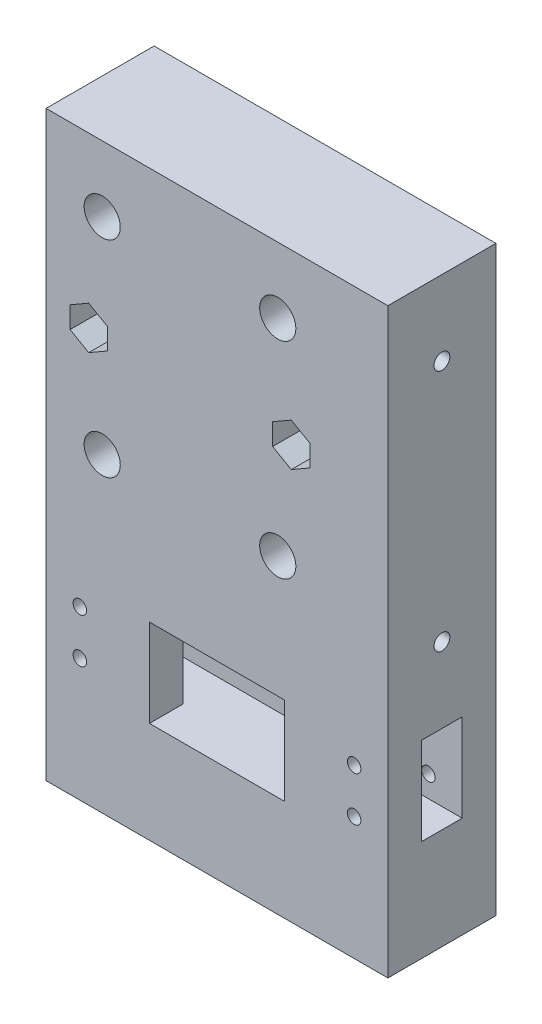
SolidWorks part; units mm, degrees
other "Markup1"
sketch "Sketch8" plane through (21.3115, 25, 0) normal (0.306, 0.1864, -0.9336) x (-0.9512, 0.0181, -0.3081)
ref_plane "Front Plane" through (0, 0, 0) normal (0, 0, 1) x (1, 0, 0)
ref_plane "Top Plane" through (0, 0, 0) normal (0, 1, 0) x (1, 0, 0)
ref_plane "Right Plane" through (0, 0, 0) normal (1, 0, 0) x (0, 0, -1)
sketch "Sketch1" plane through (0, 0, 0) normal (0, 0, 1) x (1, 0, 0)
  line L0 (0, 25) -> (0, -25) construction
  line L1 (21.3115, 25) -> (-21.3115, 25)
  line L2 (21.3115, 25) -> (21.3115, -25)
  line L3 (21.3115, -25) -> (-21.3115, -25)
  line L4 (-21.3115, 25) -> (-21.3115, -25)
  line L5 (21.3115, 25) -> (-21.3115, -25) construction
  line L6 (21.3115, -25) -> (-21.3115, 25) construction
  line L7 (-21.3115, 0) -> (21.3115, 0) construction
  circle A0 centre (-13, -15.25) radius 2.677
  circle A1 centre (13, -15.25) radius 2.677
  circle A2 centre (13, 15.25) radius 2.677
  circle A3 centre (-13, 15.25) radius 2.677
  point P0 (0, 0)
  dimension "D1" = 30.5
  dimension "D2" = 26
  dimension "D3" = 50
extrude "Boss-Extrude1" add sketch "Sketch1" along normal blind 16
sketch "Sketch2" plane through (0, 0, 0) normal (0, 0, 1) x (1, 0, 0)
  circle A0 centre (0, 0) radius 11
  dimension "D1" = 22
extrude "Cut-Extrude2" cut sketch "Sketch2" along normal blind 11
sketch "Sketch3" plane through (0, 0, 0) normal (0, 0, -1) x (-1, 0, 0)
  line L0 (0, 0) -> (-18.0234, 0) construction
  line L1 (0, 0) -> (0, 5.0894) construction
  circle A0 centre (-15, 0) radius 1.75
  circle A1 centre (15, 0) radius 1.75
  dimension "D1" = 15
  dimension "D2" = 3.5
extrude "Cut-Extrude3" cut sketch "Sketch3" against normal blind 10
sketch "Sketch9" plane through (0, 0, 0) normal (0, 0, -1) x (-1, 0, 0)
  line L0 (0, -11) -> (0, 11) construction
  line L1 (-15, 3.1754) -> (-17.75, 1.5877)
  line L2 (-17.75, 1.5877) -> (-17.75, -1.5877)
  line L3 (-17.75, -1.5877) -> (-15, -3.1754)
  line L4 (-15, -3.1754) -> (-12.25, -1.5877)
  line L5 (-12.25, -1.5877) -> (-12.25, 1.5877)
  line L6 (-12.25, 1.5877) -> (-15, 3.1754)
  line L7 (12.25, 1.5877) -> (15, 3.1754)
  line L8 (12.25, -1.5877) -> (12.25, 1.5877)
  line L9 (15, -3.1754) -> (12.25, -1.5877)
  line L10 (17.75, -1.5877) -> (15, -3.1754)
  line L11 (17.75, 1.5877) -> (17.75, -1.5877)
  line L12 (15, 3.1754) -> (17.75, 1.5877)
  circle A0 centre (-15, 0) radius 2.75 construction
  circle A1 centre (0, 0) radius 11 construction
  point P1 (-17.75, 0)
  dimension "D1" = 5.5
extrude "Cut-Extrude6" cut sketch "Sketch9" against normal through all from offset 5 offset against normal yes
sketch "Sketch30" plane through (0, -25, 0) normal (0, -1, 0) x (1, 0, 0)
  line L1 (-21.3115, 16) -> (21.3115, 16)
  line L2 (-21.3115, 16) -> (-21.3115, 0)
  line L3 (-21.3115, 0) -> (21.3115, 0)
  line L4 (21.3115, 16) -> (21.3115, 0)
extrude "Boss-Extrude8" add sketch "Sketch30" along normal blind 5.23
sketch "Sketch10" plane through (0, 0, 0) normal (0, 0, 1) x (1, 0, 0)
  line L0 (21.3115, -30.23) -> (-21.3115, -30.23)
  line L2 (-21.3115, -30.23) -> (-21.3115, -46.23)
  line L3 (-21.3115, -46.23) -> (21.3115, -46.23)
  line L4 (21.3115, -46.23) -> (21.3115, -30.23)
  point P3 (0, 0)
  dimension "D1" = 16
extrude "Boss-Extrude2" add sketch "Sketch10" along normal up to surface (16 mm away) up to face at (15, 0, 16)
sketch "Sketch14" plane through (-21.3115, 0, 0) normal (-1, 0, 0) x (0, 0, 1)
  line L0 (16, -46.23) -> (0, -46.23) construction
  line L1 (5, -46.23) -> (11, -46.23)
  line L2 (5, -46.23) -> (5, -33.23)
  line L3 (5, -33.23) -> (11, -33.23)
  line L4 (11, -46.23) -> (11, -33.23)
  line L7 (0, -46.23) -> (16, -46.23) construction
  point P6 (8, -46.23)
  point P7 (8, -46.23)
  dimension "D1" = 13
  dimension "D2" = 6
extrude "Cut-Extrude7" cut sketch "Sketch14" against normal through all
sketch "Sketch16" plane through (21.3115, 0, 0) normal (1, 0, 0) x (0, 0, -1)
  line L0 (-8, -33.23) -> (-8, 25)
  line L1 (-11, -33.23) -> (-5, -33.23) construction
  line L2 (-16, 25) -> (0, 25) construction
  line L4 (-16, 25) -> (0, 25)
  line L5 (-16, 25) -> (-16, -33.23)
  line L6 (-16, -33.23) -> (0, -33.23)
  line L7 (0, 25) -> (0, -33.23)
  line M6 (-11, -33.23) -> (-5, -33.23)
  line M9 (0, -46.23) -> (0, 25)
  line M10 (0, 25) -> (-16, 25)
  line M11 (-16, 25) -> (-16, -46.23)
extrude "Boss-Extrude3" add sketch "Sketch16" along normal blind 8 contours L6 L0 M11 M6 M10 | L6 L0 M6 M9 M10 region at (21.3115, -4.115, 12) region at (21.3115, -4.115, 4)
sketch "Sketch17" plane through (29.3115, 0, 0) normal (1, 0, 0) x (0, 0, -1)
  line L0 (-8, -33.23) -> (-8, 25)
  line L1 (-16, -33.23) -> (0, -33.23) construction
  line L2 (0, 25) -> (-16, 25) construction
  line L3 (-8, -4.115) -> (0, -4.115)
  line L4 (0, -33.23) -> (0, 25) construction
  circle A0 centre (-8, 13.885) radius 1.175
  circle A1 centre (-8, -22.115) radius 1.175
  point P8 (-8, -4.115)
  dimension "D2" = 2.35
  dimension "D1" = 18
extrude "Cut-Extrude9" cut sketch "Sketch17" against normal blind 8 contours L0 A0 | L0 A0 | A1 L0 | A1 L0 region at (29.3115, -22.115, 8.4987) region at (29.3115, 13.885, 8.4987) region at (29.3115, 13.885, 7.5013) region at (29.3115, -22.115, 7.5013)
sketch "Sketch18" plane through (0, 0, 0) normal (0, 0, -1) x (-1, 0, 0)
  line L0 (-25.3115, -33.23) -> (-25.3115, 25)
  line L1 (-29.3115, -33.23) -> (-21.3115, -33.23) construction
  line L2 (-29.3115, 25) -> (21.3115, 25) construction
  line L3 (-25.3115, -4.115) -> (-29.3115, -4.115)
  line L4 (-26.2115, 15.885) -> (-24.4115, 15.885)
  line L5 (-26.2115, 15.885) -> (-26.2115, 11.885)
  line L6 (-26.2115, 11.885) -> (-24.4115, 11.885)
  line L7 (-24.4115, 15.885) -> (-24.4115, 11.885)
  line L8 (-26.2115, 15.885) -> (-24.4115, 11.885) construction
  line L9 (-26.2115, 11.885) -> (-24.4115, 15.885) construction
  line L10 (-29.3115, -33.23) -> (-29.3115, 25) construction
  line L11 (-26.2115, -20.115) -> (-24.4115, -20.115)
  line L12 (-24.4115, -24.115) -> (-24.4115, -20.115)
  line L13 (-26.2115, -24.115) -> (-24.4115, -24.115)
  line L14 (-26.2115, -24.115) -> (-26.2115, -20.115)
  point P6 (-25.3115, 13.885)
  point P11 (-25.3115, -4.115)
  dimension "D1" = 18
  dimension "D2" = 4
  dimension "D3" = 1.8
extrude "Cut-Extrude10" cut sketch "Sketch18" against normal blind 10.2 contours L7 L4 L0 L6 | L5 L6 L0 L4 | L14 L11 L12 L13 region at (25.7615, 13.885, 0) region at (24.8615, 13.885, 0)
sketch "Sketch15" plane through (0, 0, 0) normal (0, 0, -1) x (-1, 0, 0)
  line L0 (21.3115, -46.23) -> (-21.3115, -46.23) construction
  line L1 (-29.3115, -23.2996) -> (21.3115, -23.2996)
  line L2 (-21.3115, -46.23) -> (-21.3115, -33.23)
  line L3 (-29.3115, -33.23) -> (-29.3115, 25) construction
  line L4 (-4, -23.2996) -> (-4, -46.23)
  line L7 (-21.3115, -46.23) -> (-21.3115, -33.23) construction
  line L8 (-21.3115, -33.23) -> (-21.3115, -46.23) construction
  line L9 (-21.3115, -39.73) -> (21.3115, -39.73)
  line L10 (21.3115, 25) -> (21.3115, -46.23) construction
  line L11 (21.3115, -39.73) -> (21.3115, -28)
  line L12 (21.3115, -28) -> (0, -28)
  line L13 (0, -28) -> (0, -46.23)
  circle A2 centre (16.3115, -43.03) radius 1
  circle A4 centre (16.3115, -36.43) radius 1
  point P11 (-21.3115, -46.23)
  dimension "D1" = 5
  dimension "D2" = 3.2
extrude "Cut-Extrude8" cut sketch "Sketch15" against normal through all and the other way through all contours A2 | A4
sketch "Sketch6" plane through (0, -33.23, 0) normal (0, -1, 0) x (1, 0, 0)
  line L0 (21.3115, 11) -> (-21.3115, 11) construction
  line L1 (4.517, 11) -> (-4.517, 11)
  line L2 (4.517, 11) -> (4.517, 13.3875)
  line L3 (4.517, 13.3875) -> (-4.517, 13.3875)
  line L4 (-4.517, 11) -> (-4.517, 13.3875)
  line L5 (4.517, 11) -> (-4.517, 13.3875) construction
  line L6 (4.517, 13.3875) -> (-4.517, 11) construction
  point P0 (0, 12.1938)
  point P5 (-1.4099, 31.1844)
  point P9 (0, 0)
extrude "Cut-Extrude5" cut sketch "Sketch6" against normal blind 30 and the other way through all
sketch "Sketch20" plane through (0, -33.23, 0) normal (0, -1, 0) x (-1, 0, 0)
  line L1 (-21.3115, -16) -> (-29.3115, -16)
  line L2 (-21.3115, -16) -> (-21.3115, 0)
  line L3 (-21.3115, 0) -> (-29.3115, 0)
  line L4 (-29.3115, -16) -> (-29.3115, 0)
extrude "Boss-Extrude5" add sketch "Sketch20" along normal up to surface (13 mm away) up to face at (0, -46.23, 12.8469)
sketch "Sketch21" plane through (0, -46.23, 0) normal (0, -1, 0) x (-1, 0, 0)
  line L0 (-29.3115, -16) -> (-29.3115, 0) construction
  line L1 (-21.3115, -11) -> (-29.3115, -11)
  line L2 (-21.3115, -11) -> (-21.3115, -5)
  line L3 (-21.3115, -5) -> (-29.3115, -5)
  line L4 (-29.3115, -11) -> (-29.3115, -5)
extrude "Cut-Extrude11" cut sketch "Sketch21" against normal up to surface (13 mm away) up to face at (0, -33.23, 9)
sketch "Sketch22" plane through (0, 0, 0) normal (0, 0, -1) x (-1, 0, 0)
  line L0 (21.3115, -46.23) -> (-29.3115, -46.23) construction
  line L1 (-29.3115, -46.23) -> (-29.3115, 25) construction
  circle A0 centre (-24.3115, -43.03) radius 1
  circle A3 centre (-24.3115, -36.43) radius 1
  dimension "D1" = 2
  dimension "D2" = 3.2
  dimension "D3" = 5
  dimension "D4" = 6.6
  dimension "D5" = 2
  dimension "D6" = 5
extrude "Cut-Extrude12" cut sketch "Sketch22" against normal through all
sketch "Sketch24" plane through (0, -46.23, 0) normal (0, -1, 0) x (1, 0, 0)
  line L1 (-21.3115, 5) -> (29.3115, 5)
  line L2 (-21.3115, 5) -> (-21.3115, 0)
  line L3 (-21.3115, 0) -> (29.3115, 0)
  line L4 (29.3115, 5) -> (29.3115, 0)
extrude "Boss-Extrude6" add sketch "Sketch24" along normal blind 15
sketch "Sketch25" plane through (0, 0, 5) normal (0, 0, 1) x (1, 0, 0)
  line L0 (29.3115, -61.23) -> (-21.3115, -61.23) construction
  line L1 (-21.3115, -61.23) -> (29.3115, -61.23)
  line L2 (-21.3115, -61.23) -> (-21.3115, -46.23)
  line L3 (-21.3115, -46.23) -> (29.3115, -46.23)
  line L4 (29.3115, -61.23) -> (29.3115, -46.23)
extrude "Boss-Extrude7" add sketch "Sketch25" along normal up to surface (11 mm away) up to face at (23.3115, -43.03, 16)
sketch "Sketch26" plane through (0, -61.23, 0) normal (0, -1, 0) x (1, 0, 0)
  line L0 (4, 16) -> (4, 0)
  line L1 (29.3115, 16) -> (-21.3115, 16) construction
  line L2 (-21.3115, 0) -> (29.3115, 0) construction
  line L3 (4, 8) -> (-21.3115, 8)
  line L4 (-21.3115, 16) -> (-21.3115, 0) construction
  circle A0 centre (-14, 8) radius 1
  circle A1 centre (22, 8) radius 1
  dimension "D1" = 2
  dimension "D2" = 18
extrude "Cut-Extrude13" cut sketch "Sketch26" against normal blind 10 contours L3 A0 | L3 A0 | A1 region at (-14, -61.23, 7.5756) region at (-14, -61.23, 8.4244) region at (22, -61.23, 8)
sketch "Sketch27" plane through (0, 0, 0) normal (0, 0, -1) x (-1, 0, 0)
  line L0 (-24.4115, -24.115) -> (-24.4115, -20.115) construction
  line L1 (-24.0015, -56.33) -> (-20.0015, -56.33)
  line L2 (-24.0015, -56.33) -> (-24.0015, -58.13)
  line L3 (-24.0015, -58.13) -> (-20.0015, -58.13)
  line L4 (-20.0015, -56.33) -> (-20.0015, -58.13)
  line L5 (-24.0015, -56.33) -> (-20.0015, -58.13) construction
  line L6 (-24.0015, -58.13) -> (-20.0015, -56.33) construction
  line L8 (-26.2115, -24.115) -> (-24.4115, -24.115) construction
  line L12 (-29.3115, -61.23) -> (-29.3115, 25) construction
  line L13 (21.3115, -61.23) -> (-29.3115, -61.23) construction
  line L14 (-29.3115, -49.5626) -> (21.3115, -49.5626)
  line L15 (21.3115, 25) -> (21.3115, -61.23) construction
  line L16 (-4, -49.5626) -> (-4, -61.23)
  line L17 (16.0015, -58.13) -> (12.0015, -58.13)
  line L18 (12.0015, -56.33) -> (12.0015, -58.13)
  line L19 (16.0015, -56.33) -> (12.0015, -56.33)
  line L20 (16.0015, -56.33) -> (16.0015, -58.13)
  point P0 (-22.0015, -57.23)
  dimension "D1" = 7.31
  dimension "D2" = 3.1
extrude "Cut-Extrude14" cut sketch "Sketch27" against normal blind 10.2 contours L4 L1 L2 L3 | L20 L19 L18 L17 region at (22.0015, -57.23, 0) region at (-14.0015, -57.23, 0)
sketch "Sketch29" plane through (0, 0, 16) normal (0, 0, 1) x (1, 0, 0)
  line L0 (-16.3115, -36.43) -> (24.3115, -43.03)
  line L1 (24.3115, -36.43) -> (-16.3115, -43.03)
  line L2 (-16.3115, -36.43) -> (24.3115, -36.43)
  line L3 (-16.3115, -36.43) -> (-16.3115, -43.03)
  line L4 (-16.3115, -43.03) -> (24.3115, -43.03)
  line L5 (24.3115, -36.43) -> (24.3115, -43.03)
  line L7 (-6, -33.23) -> (14, -33.23)
  line L8 (-6, -33.23) -> (-6, -46.23)
  line L9 (-6, -46.23) -> (14, -46.23)
  line L10 (14, -33.23) -> (14, -46.23)
  line L11 (-6, -33.23) -> (14, -46.23) construction
  line L12 (-6, -46.23) -> (14, -33.23) construction
  circle A0 centre (-16.3115, -36.43) radius 1 construction
  point P4 (4, -39.73)
  point P11 (0, 0)
  dimension "D1" = 13
  dimension "D2" = 20
extrude "Cut-Extrude15" cut sketch "Sketch29" against normal up to surface (5 mm away) contours L10 L7 L8 L2 | L10 L2 L8 L0 L1 | L0 L8 L1 | L10 L4 L8 L9 | L10 L0 L1 L8 L4 | L10 L1 L0 region at (4, -37.718, 16) region at (-2.6667, -39.73, 16) region at (4, -34.83, 16) region at (10.6667, -39.73, 16) region at (4, -41.742, 16) region at (4, -44.63, 16) up to face at (-16.3115, -44.03, 11)
